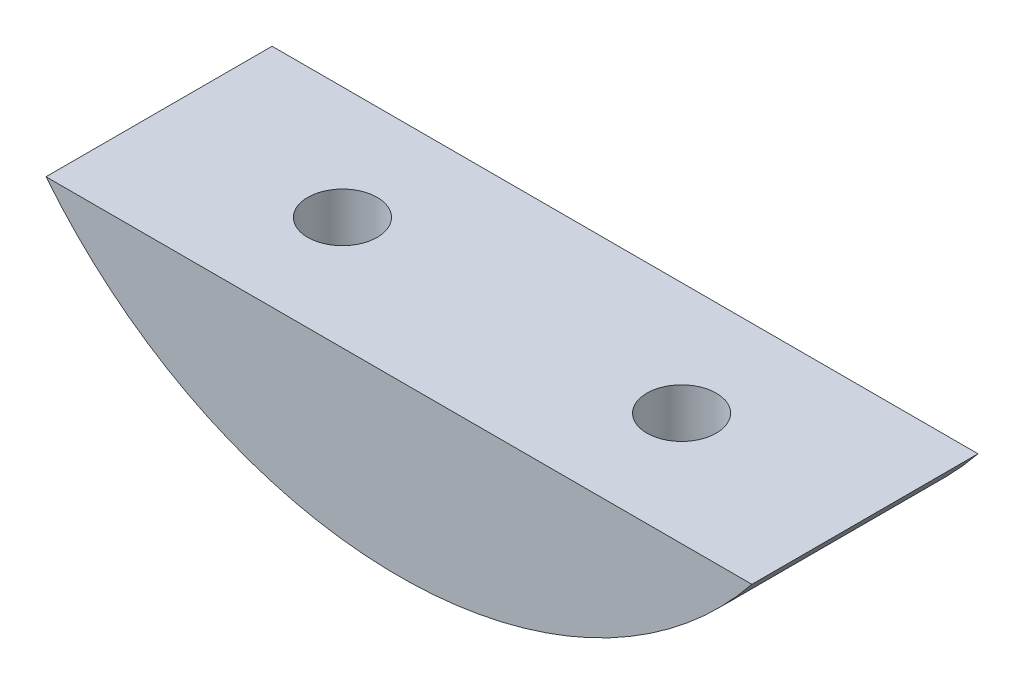
SolidWorks part; units mm, degrees
ref_plane "Front Plane" through (0, 0, 0) normal (0, 0, 1) x (1, 0, 0)
ref_plane "Top Plane" through (0, 0, 0) normal (0, 1, 0) x (1, 0, 0)
ref_plane "Right Plane" through (0, 0, 0) normal (1, 0, 0) x (0, 0, -1)
sketch "Sketch1" plane through (0, 0, 0) normal (0, 0, 1) x (1, 0, 0)
  line L0 (0, 0) -> (79.3115, 0)
  arc A0 (0, 0) -> (79.3115, 0) centre (39.6557, 31.75) ccw
  dimension "D1" = 50.8
  dimension "D2" = 31.75
extrude "Boss-Extrude1" add sketch "Sketch1" along normal blind 25.4
sketch "Sketch2" plane through (0, 0, 0) normal (0, 1, 0) x (1, 0, 0)
  line L0 (0, -12.7) -> (20.6057, -12.7) construction
  line L1 (0, -25.4) -> (0, 0) construction
  line L2 (20.6057, -12.7) -> (58.7057, -12.7) construction
  line L3 (58.7057, -12.7) -> (79.3115, -12.7) construction
  line L4 (79.3115, -25.4) -> (79.3115, 0) construction
  circle A0 centre (20.6057, -12.7) radius 2.5
  circle A1 centre (58.7057, -12.7) radius 2.5
  dimension "D2" = 5
  dimension "D1" = 38.1
extrude "Cut-Extrude1" cut sketch "Sketch2" against normal through all both and the other way through all
sketch "Sketch3" plane through (0, 0, 0) normal (0, 1, 0) x (1, 0, 0)
  circle A0 centre (20.6057, -12.7) radius 3.9
  circle A1 centre (58.7057, -12.7) radius 3.9
  dimension "D1" = 7.8
extrude "Cut-Extrude2" cut sketch "Sketch3" against normal blind 6.8
